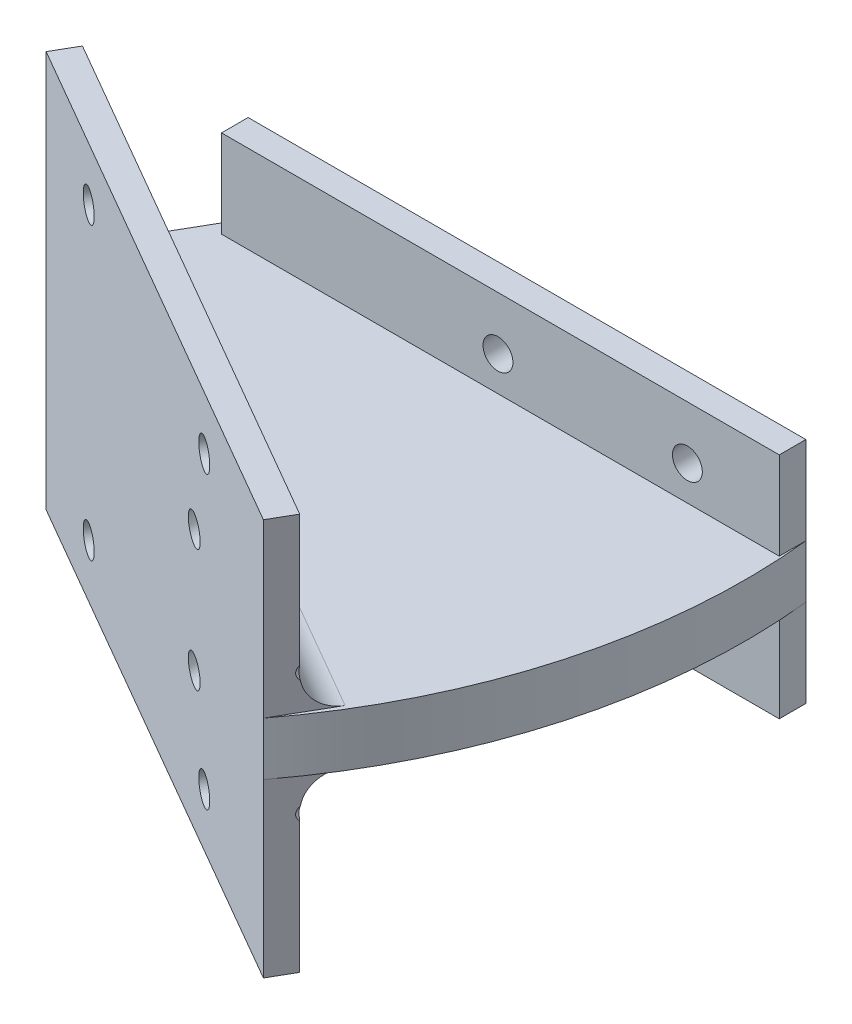
SolidWorks part; units mm, degrees
ref_plane "Front Plane" through (0, 0, 0) normal (0, 0, 1) x (1, 0, 0)
ref_plane "Top Plane" through (0, 0, 0) normal (0, 1, 0) x (1, 0, 0)
ref_plane "Right Plane" through (0, 0, 0) normal (1, 0, 0) x (0, 0, -1)
sketch "Sketch2" plane through (0, 0, 0) normal (0, 1, 0) x (1, 0, 0)
  line L0 (1.1547, 0) -> (85.0762, 0)
  line L1 (22, 0) -> (108, 0) construction
  line L2 (1.1547, 0) -> (-9.9683, -19.2656)
  line L3 (-9.9683, -19.2656) -> (67.3765, -63.9206)
  line L4 (89.6246, -76.7656) -> (-61.9298, 10.7344) construction
  line L6 (-205.4298, -237.8149) -> (19.5702, 151.8966) construction
  arc A0 (85.0762, 0) -> (67.3765, -63.9206) centre (-4.4068, -9.6328) cw
  dimension "D2" = 0
  dimension "D4" = 90
  dimension "D1" = 30
  dimension "D3" = 60
extrude "Boss-Extrude1" add sketch "Sketch2" along normal blind 4 and the other way blind 4
sketch "Sketch3" plane through (-10.8343, 0, 18.7656) normal (-0.5, 0, 0.866) x (0.866, 0, 0.5)
  line L0 (90.31, -4) -> (90.31, 4) construction
  line L1 (1, 29.8583) -> (90.31, 29.8583)
  line L2 (1, 29.8583) -> (1, -29.8583)
  line L3 (1, -29.8583) -> (90.31, -29.8583)
  line L4 (90.31, 29.8583) -> (90.31, -29.8583)
  line L5 (1, -4) -> (1, 4) construction
  circle A0 centre (66, -21.8583) radius 2.1 construction
  circle A1 centre (66, 21.8583) radius 2.1 construction
  dimension "D1" = 8
  dimension "D2" = 8
extrude "Boss-Extrude2" add sketch "Sketch3" against normal blind 4
sketch "Sketch4" plane through (-10.8343, 0, 18.7656) normal (-0.5, 0, 0.866) x (0.866, 0, 0.5)
  circle A0 centre (66, 21.8583) radius 2.25
  circle A1 centre (66, -21.8583) radius 2.25
  circle A2 centre (18.5, 21.8583) radius 2.25
  circle A3 centre (18.5, -21.8583) radius 2.25
  dimension "D1" = 4.5
  dimension "D2" = 4.5
  dimension "D3" = 4.5
  dimension "D4" = 4.5
extrude "Cut-Extrude1" cut sketch "Sketch4" against normal up to next
sketch "Sketch5" plane through (0, 0, 0) normal (0, 0, -1) x (-1, 0, 0)
  line L0 (-1.1547, -4) -> (-1.1547, 4) construction
  line L1 (-85.0762, -17.2) -> (-1.1547, -17.2)
  line L2 (-85.0762, -17.2) -> (-85.0762, 17.2)
  line L3 (-85.0762, 17.2) -> (-1.1547, 17.2)
  line L4 (-1.1547, -17.2) -> (-1.1547, 17.2)
  line L5 (-85.0762, -4) -> (-85.0762, 4) construction
  circle A0 centre (-71.25, 9.2) radius 2 construction
  circle A1 centre (-71.25, -9.2) radius 2 construction
  dimension "D1" = 8
  dimension "D2" = 8
extrude "Boss-Extrude3" add sketch "Sketch5" against normal blind 4
sketch "Sketch6" plane through (0, 0, 0) normal (0, 0, -1) x (-1, 0, 0)
  circle A0 centre (-71.25, -9.2) radius 2.25
  circle A1 centre (-71.25, 9.2) radius 2.25
  circle A2 centre (-42.75, 9.2) radius 2.25
  circle A4 centre (-42.75, -9.2) radius 2.25
  circle A5 centre (-42.75, 9.2) radius 2 construction
  dimension "D1" = 4.5
  dimension "D2" = 4.5
  dimension "D3" = 4.5
  dimension "D4" = 4.5
extrude "Cut-Extrude2" cut sketch "Sketch6" against normal blind 4
fillet "Fillet1" radius 5 2 edges at (30.7041, -4, 38.129) (30.7041, 4, 38.129)
sketch "Sketch7" plane through (0, 0, 4) normal (0, 0, 1) x (1, 0, 0)
  circle A0 centre (42.75, 9.2) radius 2.1
  circle A1 centre (71.25, 9.2) radius 2.1
  dimension "D1" = 4.2
  dimension "D2" = 4.2
extrude "Cut-Extrude3" cut sketch "Sketch7" along normal through all
mirror "Mirror1" about plane through (0, 0, 0) normal (0, 1, 0) of "Cut-Extrude3"
